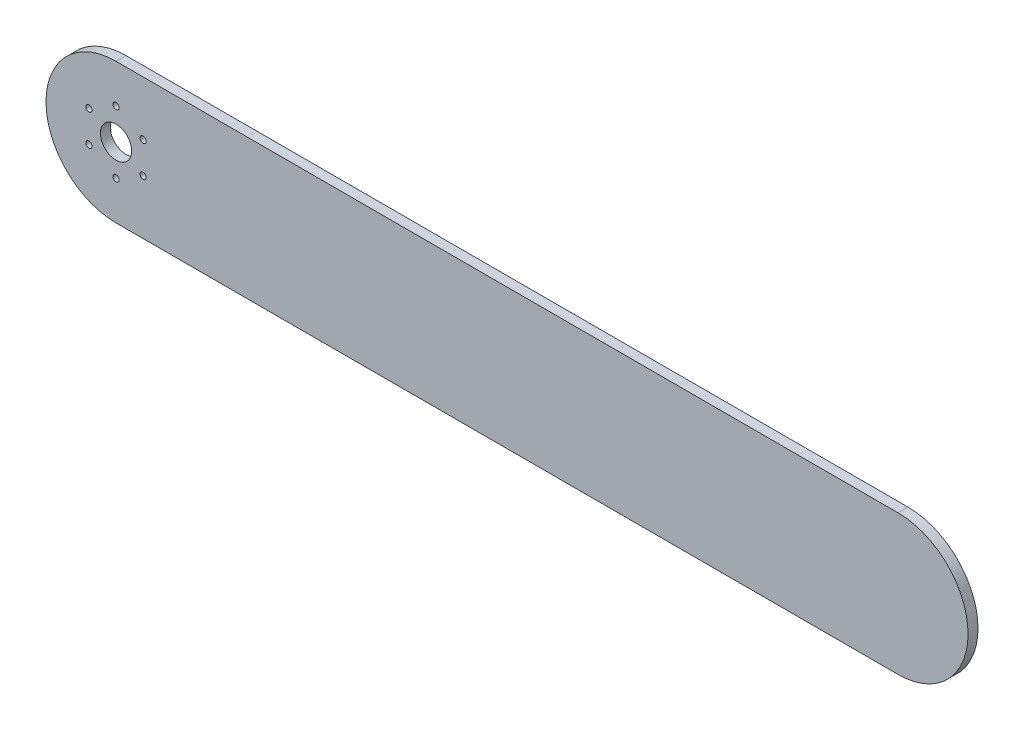
SolidWorks part; units mm, degrees
ref_plane "Front Plane" through (0, 0, 0) normal (0, 0, 1) x (1, 0, 0)
ref_plane "Top Plane" through (0, 0, 0) normal (0, 1, 0) x (1, 0, 0)
ref_plane "Right Plane" through (0, 0, 0) normal (1, 0, 0) x (0, 0, -1)
sketch "Sketch2" plane through (0, 0, 0) normal (0, 0, 1) x (1, 0, 0)
  line L0 (0, 0) -> (500, 0) construction
  line L1 (0, 44.75) -> (500, 44.75)
  line L2 (0, -44.75) -> (500, -44.75)
  arc A0 (0, 44.75) -> (0, -44.75) centre (0, 0) ccw
  arc A1 (500, -44.75) -> (500, 44.75) centre (500, 0) ccw
  circle A2 centre (500, 0) radius 37.25 construction
  circle A3 centre (0, 0) radius 10
  circle A4 centre (0, 20) radius 2
  circle A5 centre (0, 0) radius 20 construction
  circle A6 centre (17.3205, 10) radius 2
  circle A7 centre (17.3205, -10) radius 2
  circle A8 centre (0, -20) radius 2
  circle A9 centre (-17.3205, -10) radius 2
  circle A10 centre (-17.3205, 10) radius 2
  point P3 (250, 0)
  point P16 (0, 0)
  point P17 (0, 0)
  point P27 (0, 0)
  dimension "D2" = 74.5
  dimension "D4" = 20
  dimension "D5" = 4
  dimension "D6" = 40
  dimension "D1" = 500
  dimension "D3" = 7.5
  dimension "D7" = 6
extrude "Boss-Extrude1" add sketch "Sketch2" along normal blind 6.35
equation "\"L1L\"=500"
equation "\"L1Thick\"=6.35"
equation "\"D1@Sketch2\"=\"L1L\""
equation "\"Harm-Drive-Outer\"=74.5"
equation "\"D2@Sketch2\"=\"Harm-Drive-Outer\""
equation "\"D1@Boss-Extrude1\"=\"L1Thick\""
